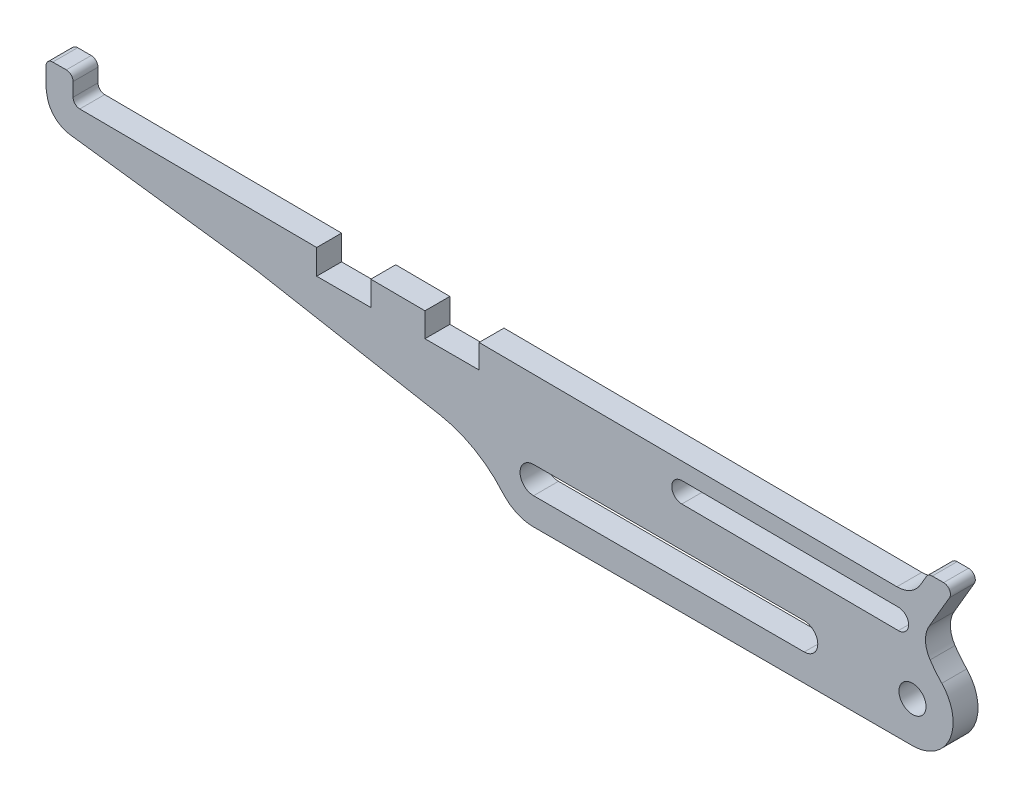
SolidWorks part; units mm, degrees
ref_plane "Front Plane" through (0, 0, 0) normal (0, 0, 1) x (1, 0, 0)
ref_plane "Top Plane" through (0, 0, 0) normal (0, 1, 0) x (1, 0, 0)
ref_plane "Right Plane" through (0, 0, 0) normal (1, 0, 0) x (0, 0, -1)
sketch "Sketch1" plane through (0, 0, 0) normal (0, 0, 1) x (1, 0, 0)
  line L0 (44.45, 0) -> (-44.45, 0) construction
  line L1 (44.45, -9.525) -> (-44.45, -9.525)
  line L2 (-158.75, 22.225) -> (44.45, 20.9214)
  line L3 (44.45, 0) -> (-44.45, 0) construction
  line L4 (19.05, -3.175) -> (-44.45, -3.175)
  line L5 (19.05, 3.175) -> (-44.45, 3.175)
  line L7 (-158.75, 22.225) -> (-158.75, 19.05)
  line L8 (44.45, 9.525) -> (44.45, 20.9214)
  line L9 (-53.975, 0) -> (-158.75, 19.05)
  line L11 (44.45, 9.525) -> (-158.75, 34.925) construction
  line L12 (44.45, 34.925) -> (-158.75, 9.525) construction
  arc A0 (44.45, -9.525) -> (44.45, 9.525) centre (44.45, 0) ccw
  arc A1 (-53.975, 0) -> (-44.45, -9.525) centre (-44.45, 0) ccw
  circle A2 centre (44.45, 0) radius 3.175
  arc A3 (-44.45, 3.175) -> (-44.45, -3.175) centre (-44.45, 0) ccw
  arc A4 (19.05, -3.175) -> (19.05, 3.175) centre (19.05, 0) ccw
  point P2 (0, 0)
  point P10 (0, 0)
  point P19 (-57.15, 22.225)
  dimension "D2" = 9.525
  dimension "D3" = 3.175
  dimension "D1" = 88.9
  dimension "D4" = 203.2
  dimension "D5" = 25.4
  dimension "D6" = 63.5
extrude "Boss-Extrude1" add sketch "Sketch1" along normal blind 5.842
fillet "Fillet1" radius 25.4 1 edges at (44.45, 9.525, 2.921)
sketch "Sketch2" plane through (0, 0, 5.842) normal (0, 0, 1) x (1, 0, 0)
  line L0 (-158.8317, 22.1848) -> (-158.8317, 28.5348)
  line L1 (-158.8317, 28.5348) -> (-152.4817, 28.5348)
  line L2 (-152.4817, 28.5348) -> (-152.4817, 22.1848)
  line L3 (44.45, 20.9214) -> (-158.75, 22.225) construction
  line L4 (-152.4817, 22.1848) -> (-158.8317, 22.1848)
  dimension "D1" = 6.35
  dimension "D2" = 6.35
extrude "Boss-Extrude2" add sketch "Sketch2" against normal up to surface (5.842 mm away) up to face at (47.625, 0, 0)
fillet "Fillet4" radius 1.5875 4 edges at (-158.8317, 28.5348, 2.921) (-152.4817, 28.5348, 2.921) (-158.8317, 22.1848, 2.921) (-152.4817, 22.1848, 2.921)
fillet "Fillet5" radius 25.4 1 edges at (-53.975, 0, 2.921)
fillet "Fillet6" radius 6.35 1 edges at (-158.75, 19.05, 2.921)
sketch "Sketch3" plane through (0, 0, 5.842) normal (0, 0, 1) x (1, 0, 0)
  line L0 (44.45, 20.9214) -> (-150.9044, 22.1747) construction
  line L1 (-82.6317, 15.9762) -> (-95.3317, 15.9762)
  line L2 (-82.6317, 15.9762) -> (-82.6317, 21.8182)
  line L3 (-82.6317, 21.8182) -> (-95.3317, 21.8182)
  line L4 (-95.3317, 15.9762) -> (-95.3317, 21.8182)
  line L5 (-82.6317, 15.9762) -> (-95.3317, 21.8182) construction
  line L6 (-82.6317, 21.8182) -> (-95.3317, 15.9762) construction
  line L7 (-158.8317, 26.9473) -> (-158.8317, 22.6876) construction
  line L8 (-57.2317, 15.9762) -> (-69.9317, 15.9762)
  line L9 (-57.2317, 15.9762) -> (-57.2317, 21.8182)
  line L10 (-69.9317, 15.9762) -> (-69.9317, 21.8182)
  line L11 (-57.2317, 21.8182) -> (-69.9317, 21.8182)
  point P0 (-88.9817, 18.8972)
  point P7 (-158.8317, 24.8174)
  dimension "D1" = 5.842
  dimension "D2" = 12.7
  dimension "D3" = 63.5
  dimension "D4" = 2
extrude "Cut-Extrude1" cut sketch "Sketch3" against normal through all
sketch "Sketch4" plane through (0, 0, 5.842) normal (0, 0, 1) x (1, 0, 0)
  line L0 (44.45, 20.9214) -> (48.1707, 27.2714)
  line L1 (48.1707, 27.2714) -> (54.5207, 27.2714)
  line L2 (54.5207, 27.2714) -> (46.5407, 13.6262)
  line L3 (46.5407, 13.6262) -> (43.3627, 15.4847)
  line L4 (43.3627, 15.4847) -> (44.45, 20.9214)
  line L5 (44.45, 20.9214) -> (-57.2317, 21.5737) construction
  arc A0 (44.45, 20.9214) -> (51.3196, 6.5981) centre (69.6384, 24.1929) ccw construction
  dimension "D1" = 6.35
  dimension "D2" = 6.35
  dimension "D3" = 120
extrude "Boss-Extrude3" add sketch "Sketch4" against normal up to surface (5.842 mm away) up to face at (-88.1071, 16.1968, 0)
fillet "Fillet7" radius 6.35 2 edges at (46.5407, 13.6262, 2.921) (44.45, 20.9214, 2.921)
fillet "Fillet8" radius 1.5875 2 edges at (54.5207, 27.2714, 2.921) (48.1707, 27.2714, 2.921)
sketch "Sketch5" plane through (0, 0, 5.842) normal (0, 0, 1) x (1, 0, 0)
  line L0 (-58.8971, 15.2343) -> (65.0418, 14.4392) construction
  line L1 (41.1483, 14.5925) -> (-9.6507, 14.9184) construction
  line L2 (41.133, 12.2113) -> (-9.666, 12.5372)
  line L3 (41.1636, 16.9737) -> (-9.6354, 17.2996)
  line L6 (40.7839, 20.9449) -> (-57.2317, 21.5737) construction
  arc A0 (41.133, 12.2113) -> (41.1636, 16.9737) centre (41.1483, 14.5925) ccw
  arc A1 (-9.6354, 17.2996) -> (-9.666, 12.5372) centre (-9.6507, 14.9184) ccw
  arc A2 (48.3646, 16.7448) -> (48.5819, 9.9879) centre (53.846, 13.5392) ccw construction
  point P4 (15.7488, 14.7554)
  point P11 (47.4993, 13.335)
  dimension "D1" = 2.3813
  dimension "D2" = 50.8
  dimension "D3" = 6.35
  dimension "D4" = 57.15
extrude "Cut-Extrude2" cut sketch "Sketch5" against normal through all
sketch "Sketch6" plane through (0, 0, 5.842) normal (0, 0, 1) x (1, 0, 0)
  line L0 (-158.8112, 22.4329) -> (-157.8311, 16.4037)
  line L1 (-157.8311, 16.4037) -> (-110.1845, 10.2199)
  line L2 (-153.9437, 18.1761) -> (-66.4253, 2.2637) construction
  line L3 (-158.8112, 22.4329) -> (-110.1845, 10.2199)
  arc A0 (-158.8317, 22.6876) -> (-158.75, 22.1848) centre (-157.2442, 22.6876) ccw construction
extrude "Boss-Extrude4" add sketch "Sketch6" against normal up to surface (5.842 mm away) up to face at (15.7488, 14.7554, 0)
fillet "Fillet9" radius 6.35 1 edges at (-157.8311, 16.4037, 2.921)
fillet "Fillet10" radius 50.8 1 edges at (-110.1845, 10.2199, 2.921)
